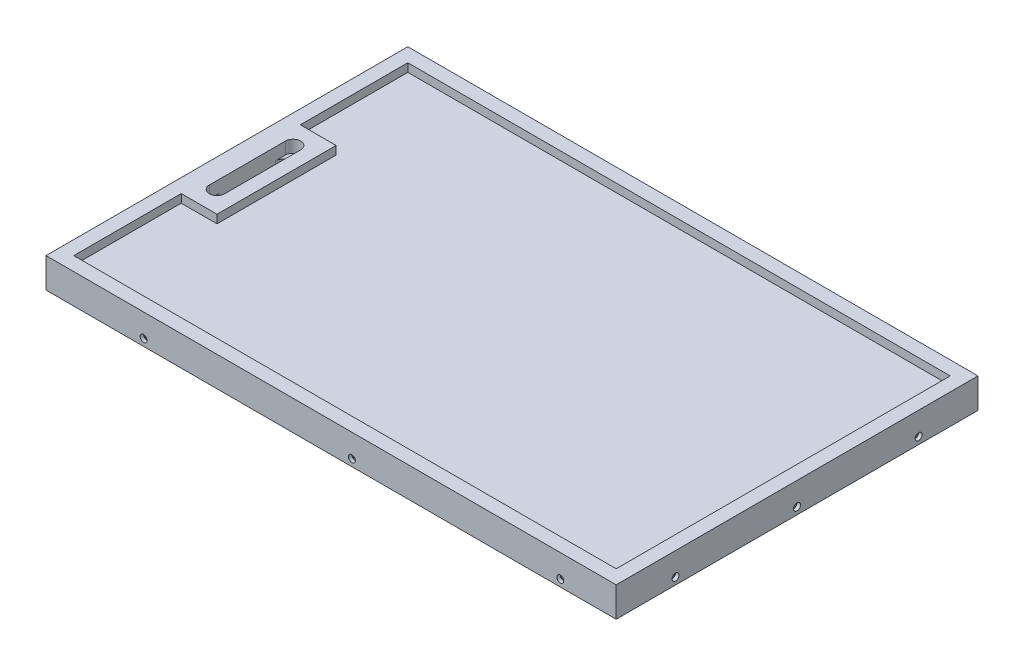
SolidWorks part; units mm, degrees
ref_plane "前视基准面" through (0, 0, 0) normal (0, 0, 1) x (1, 0, 0)
ref_plane "上视基准面" through (0, 0, 0) normal (0, 1, 0) x (1, 0, 0)
ref_plane "右视基准面" through (0, 0, 0) normal (1, 0, 0) x (0, 0, -1)
other "Configuration Table"
sketch "草图1" plane through (0, 0, 0) normal (0, 1, 0) x (1, 0, 0)
  line L1 (-82.1, -52.1) -> (82.1, -52.1)
  line L2 (-82.1, -52.1) -> (-82.1, 52.1)
  line L3 (-82.1, 52.1) -> (82.1, 52.1)
  line L4 (82.1, -52.1) -> (82.1, 52.1)
  line L5 (-82.1, -52.1) -> (82.1, 52.1) construction
  line L6 (-82.1, 52.1) -> (82.1, -52.1) construction
  dimension "D1" = 104.2
  dimension "D2" = 164.2
extrude "凸台-拉伸1" add sketch "草图1" along normal blind 8
sketch "草图2" plane through (0, 8, 0) normal (0, 1, 0) x (1, 0, 0)
  line L0 (-74, -8.05) -> (-74, 8.05) construction
  line L1 (-76.2, -8.05) -> (-76.2, 8.05)
  line L2 (-71.8, -8.05) -> (-71.8, 8.05)
  line L4 (-74, 10.95) -> (-74, -10.95) construction
  line L5 (-71.8, 10.95) -> (-71.8, -10.95)
  line L6 (-76.2, 10.95) -> (-76.2, -10.95)
  arc A0 (-76.2, -8.05) -> (-71.8, -8.05) centre (-74, -8.05) ccw
  arc A1 (-71.8, 8.05) -> (-76.2, 8.05) centre (-74, 8.05) ccw
  arc A2 (-71.8, 10.95) -> (-76.2, 10.95) centre (-74, 10.95) ccw
  arc A3 (-76.2, -10.95) -> (-71.8, -10.95) centre (-74, -10.95) ccw
  circle A4 centre (-74, 11.5) radius 0.3
  circle A5 centre (-74, -11.5) radius 0.3
  point P2 (-74, 0)
  point P9 (-74, 0)
  dimension "D3" = 16.1
  dimension "D7" = 0.6
  dimension "D1" = 74
  dimension "D2" = 4.4
  dimension "D4" = 21.9
  dimension "D5" = 11.5
  dimension "D6" = 11.5
extrude "切除-拉伸1" cut sketch "草图2" against normal through all contours A1 L1 A0 L2 | A4 | A5
extrude "切除-拉伸2" cut sketch "草图2<3>" against normal offset from surface (5.9 mm away) 2.1 contours A3 L5 A2 L6 up to face at (-74, 0, 11.8)
sketch "草图2<3>" plane through (0, 8, 0) normal (0, 1, 0) x (1, 0, 0) same geometry as "草图2"
sketch "草图3" plane through (0, 8, 0) normal (0, 1, 0) x (1, 0, 0)
  line L0 (82.1, 52.1) -> (-82.1, 52.1) construction
  line L1 (-67.8, 48.1) -> (78.1, 48.1)
  line L2 (-67.8, 48.1) -> (-67.8, -48.1)
  line L3 (-67.8, -48.1) -> (78.1, -48.1)
  line L4 (78.1, 48.1) -> (78.1, -48.1)
  line L5 (-67.8, 48.1) -> (-78.1, 48.1)
  line L6 (-67.8, 48.1) -> (-67.8, 17.15)
  line L7 (-67.8, 17.15) -> (-78.1, 17.15)
  line L8 (-78.1, 48.1) -> (-78.1, 17.15)
  line L9 (-67.8, -48.1) -> (-78.1, -48.1)
  line L10 (-67.8, -48.1) -> (-67.8, -17.15)
  line L11 (-67.8, -17.15) -> (-78.1, -17.15)
  line L12 (-78.1, -48.1) -> (-78.1, -17.15)
  line L13 (-82.1, 52.1) -> (-82.1, -52.1) construction
  line L14 (-82.1, -52.1) -> (82.1, -52.1) construction
  line L15 (82.1, -52.1) -> (82.1, 52.1) construction
  line L16 (-71.8, -10.95) -> (-71.8, 10.95) construction
  line L17 (-77.2424, 13.15) -> (-70.2936, 13.15) construction
  line L18 (-78, -13.15) -> (-70.2936, -13.15) construction
  arc A1 (-76.2, -10.95) -> (-71.8, -10.95) centre (-74, -10.95) ccw construction
  arc A2 (-71.8, 10.95) -> (-76.2, 10.95) centre (-74, 10.95) ccw construction
  dimension "D7" = 4
  dimension "D1" = 4
  dimension "D2" = 4
  dimension "D3" = 4
  dimension "D4" = 4
  dimension "D5" = 4
  dimension "D6" = 4
  dimension "D8" = 4
sketch "草图5" plane through (0, 0, 0) normal (0, -1, 0) x (1, 0, 0)
  line L0 (82.1, 52.1) -> (82.1, -52.1) construction
  line L1 (-68.2, 50.1) -> (80.2, 50.1)
  line L2 (-68.2, 50.1) -> (-68.2, -50.1)
  line L3 (-68.2, -50.1) -> (80.2, -50.1)
  line L4 (80.2, 50.1) -> (80.2, -50.1)
  line L5 (82.1, -52.1) -> (-82.1, -52.1) construction
  line L6 (-82.1, 52.1) -> (82.1, 52.1) construction
  line L7 (-82.1, -52.1) -> (-82.1, 52.1) construction
  dimension "D1" = 1.9
  dimension "D2" = 2
  dimension "D3" = 2
  dimension "D4" = 13.9
extrude "切除-拉伸5" cut sketch "草图5" against normal offset from surface (1.2 mm away) 6.8 up to face at (0, 8, 0)
sketch "草图6" plane through (0, 0, 0) normal (0, -1, 0) x (1, 0, 0)
  line L0 (-74.1, -10.95) -> (-74.1, 10.95) construction
  line L1 (-76.4, -10.95) -> (-76.4, 10.95)
  line L2 (-71.8, -10.95) -> (-71.8, 10.95)
  line L3 (-82.1, -52.1) -> (-82.1, 52.1) construction
  line L4 (-76.1, -3) -> (-76.1, 3) construction
  line L5 (-78.35, -3) -> (-78.35, 3)
  line L6 (-73.85, -3) -> (-73.85, 3)
  arc A0 (-76.4, -10.95) -> (-71.8, -10.95) centre (-74.1, -10.95) ccw
  arc A1 (-71.8, 10.95) -> (-76.4, 10.95) centre (-74.1, 10.95) ccw
  arc A3 (-78.35, -3) -> (-73.85, -3) centre (-76.1, -3) ccw
  arc A4 (-73.85, 3) -> (-78.35, 3) centre (-76.1, 3) ccw
  circle A6 centre (-72.1, 0) radius 2.25
  point P2 (-74.1, 0)
  point P7 (-76.1, 0)
  line M6 (-68.2, -50.1) -> (-68.2, 50.1)
  line M7 (-68.2, 50.1) -> (80.2, 50.1)
  line M8 (80.2, 50.1) -> (80.2, -50.1)
  line M9 (80.2, -50.1) -> (-68.2, -50.1)
  circle M10 centre (-74, 11.5) radius 0.3
  circle M11 centre (-74, -11.5) radius 0.3
  line M16 (82.1, -52.1) -> (82.1, 52.1)
  line M17 (82.1, 52.1) -> (-82.1, 52.1)
  line M18 (-82.1, 52.1) -> (-82.1, -52.1)
  line M19 (-82.1, -52.1) -> (82.1, -52.1)
  dimension "D7" = 4.5
  dimension "D1" = 8
  dimension "D2" = 4.6
  dimension "D3" = 21.9
  dimension "D4" = 6
  dimension "D5" = 6
  dimension "D6" = 4.5
  dimension "D8" = 2
extrude "凸台-拉伸2" add sketch "草图6" along normal blind 3 contours A6 L2 A0 L1 A3 L5 A4 A1 M19 M16 M17 M18 M11 M10 M9 M6 M7 M8 region at (0, 0, -50.1553)
sketch "草图7" plane through (0, 0, -50.1) normal (0, 0, 1) x (1, 0, 0)
  line L0 (6, 1.2) -> (6, -3) construction
  line L1 (80.2, -3) -> (-68.2, -3) construction
  line L2 (80.2, 1.2) -> (-68.2, 1.2) construction
  line L3 (-54, -1) -> (6, -1) construction
  line L5 (6, -1) -> (66, -1) construction
  line L6 (82.1, -3) -> (-82.1, -3) construction
  circle A0 centre (6, -1) radius 1
  circle A1 centre (-54, -1) radius 0.75
  circle A2 centre (66, -1) radius 1
  circle A3 centre (66, -1) radius 0.75
  circle A4 centre (6, -1) radius 0.75
  circle A5 centre (-54, -1) radius 1
  dimension "D1" = 1.5
  dimension "D2" = 2
  dimension "D3" = 60
  dimension "D4" = 2
extrude "切除-拉伸6" cut sketch "草图7" against normal through all both and the other way through all contours A4 | A1 | A3 region at (6, -1, -50.1)
extrude "切除-拉伸7" cut sketch "草图7<3>" along normal blind 1 from surface starting at face at (66.75, -1, -52.1)
sketch "草图7<3>" plane through (0, 0, -50.1) normal (0, 0, 1) x (1, 0, 0) same geometry as "草图7"
extrude "切除-拉伸8" cut sketch "草图7<4>" against normal blind 1 from surface starting at face at (66.75, -1, 52.1)
sketch "草图7<4>" plane through (0, 0, -50.1) normal (0, 0, 1) x (1, 0, 0) same geometry as "草图7"
sketch "草图8" plane through (80.2, 0, 0) normal (-1, 0, 0) x (0, 0, 1)
  line L0 (-35, -1) -> (0, -1) construction
  line L1 (0, -1) -> (35, -1) construction
  line L2 (0, 1.2) -> (0, -3) construction
  line L3 (50.1, 1.2) -> (-50.1, 1.2) construction
  line L4 (50.1, -3) -> (-50.1, -3) construction
  line L5 (52.1, -3) -> (-52.1, -3) construction
  circle A0 centre (0, -1) radius 1
  circle A1 centre (-35, -1) radius 1
  circle A2 centre (35, -1) radius 1
  circle A3 centre (-35, -1) radius 0.75
  circle A4 centre (0, -1) radius 0.75
  circle A5 centre (35, -1) radius 0.75
  point P17 (0, 0)
  dimension "D2" = 1.5
  dimension "D3" = 2
  dimension "D1" = 35
  dimension "D4" = 2
extrude "切除-拉伸9" cut sketch "草图8" against normal through all contours A3 | A4 | A5
extrude "切除-拉伸10" cut sketch "草图8<3>" along normal blind 1 from surface starting at face at (82.1, -1, -34.25)
sketch "草图8<3>" plane through (80.2, 0, 0) normal (-1, 0, 0) x (0, 0, 1) same geometry as "草图8"
extrude "切除-拉伸11" cut sketch "草图3" against normal offset from surface (4.8 mm away) 2 contours L4 L1 L2 L3 | L5 L8 L7 L2 | L12 L9 L2 L11 region at (5.15, 8, 0) region at (-72.95, 8, -32.625) region at (-72.95, 8, 32.625) up to face at (6, 1.2, 0)
sketch "草图9" plane through (0, 8, 0) normal (0, 1, 0) x (1, 0, 0)
  line L0 (-82.1, -52.1) -> (82.1, -52.1) construction
  line L1 (-82.1, 52.1) -> (82.1, 52.1)
  line L2 (-82.1, 52.1) -> (-82.1, -52.1)
  line L3 (-82.1, -52.1) -> (82.1, -52.1)
  line L4 (82.1, 52.1) -> (82.1, -52.1)
  line L5 (82.1, -52.1) -> (82.1, 52.1) construction
extrude "切除-拉伸12" cut sketch "草图9" against normal blind 2.4
